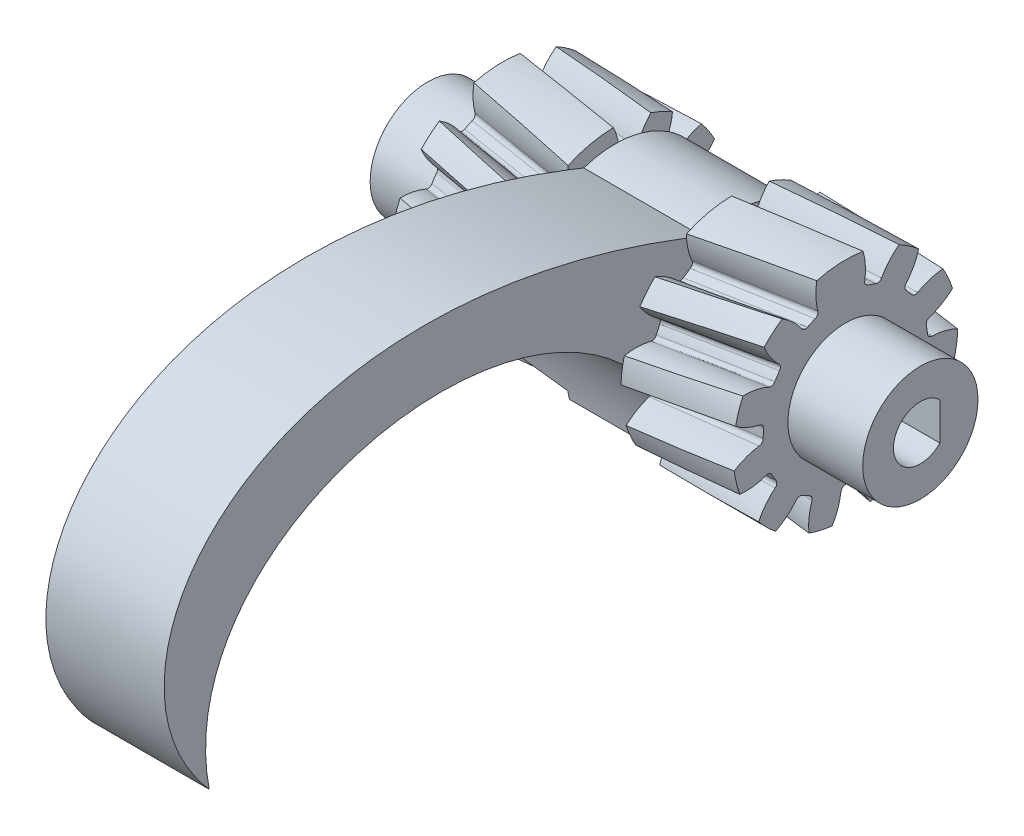
SolidWorks part; units mm, degrees
material "ABS"
ref_plane "Front Plane" through (0, 0, 0) normal (0, 0, 1) x (1, 0, 0)
ref_plane "Top Plane" through (0, 0, 0) normal (0, 1, 0) x (1, 0, 0)
ref_plane "Right Plane" through (0, 0, 0) normal (1, 0, 0) x (0, 0, -1)
sketch "Sketch1" plane through (0, 0, 0) normal (1, 0, 0) x (0, 0, -1)
  line L0 (0, 0) -> (-30, 0) construction
  line L1 (-30, 0) -> (-30, -7.5) construction
  line L2 (-30, -7.5) -> (0, 0) construction
  line L6 (-23.4, 0) -> (-23.4, -7.5) construction
  circle A2 centre (0, 0) radius 1.5 construction
  arc A3 (0, -7.5) -> (-2.4038, 7.1043) centre (0, 0) ccw
  circle A4 centre (0, 0) radius 7.5
  dimension "D2" = 3
  dimension "D4" = 7.5
  dimension "D1" = 30
  dimension "D3" = 7.5
  dimension "D5" = 6.6
extrude "ClawShape" add sketch "Sketch1" along normal mid plane 7.5
sketch "GearProfile" plane through (0, 0, 0) normal (1, 0, 0) x (0, 0, -1)
  line L0 (0, 0) -> (0, 7.5) construction
  line L1 (-0.7835, 6.4526) -> (0.7835, 6.4526) construction
  line L2 (0, 0) -> (-0.5585, 5.4716) construction
  line L3 (0, 4.3) -> (-1.4813, 8.3699) construction
  line L4 (0, 0) -> (1.7949, 7.2821) construction
  line L5 (0.7835, 6.4526) -> (2.3049, 6.0776) construction
  circle A0 centre (0, 0) radius 7.5 construction
  arc A1 (-0.5585, 5.4716) -> (-2.07, 8.2441) centre (-4.6172, 5.0573) ccw
  arc A2 (0.5585, 5.4716) -> (2.07, 8.2441) centre (4.6172, 5.0573) cw
  circle A3 centre (0, 0) radius 6.5 construction
  arc A4 (0.5585, 5.4716) -> (-0.5585, 5.4716) centre (0, 0) ccw
  circle A5 centre (0, 0) radius 2.94 construction
  arc A6 (2.07, 8.2441) -> (-2.07, 8.2441) centre (0, 0) ccw
  dimension "D3" = 5.88
  dimension "D1" = 13
  dimension "D5" = 20
  dimension "D6" = 13.846
ref_plane "Plane2" through (0, 0, 0) normal (0, 0.9709, -0.2394) x (-1, 0, 0)
sketch "Sketch4" plane through (0, 0, 0) normal (0, 1, 0) x (1, 0, 0)
  line L0 (-3.75, 7.5) -> (-3.75, -7.5) construction
  line L1 (-3.75, 0.6612) -> (3.75, -0.6612)
  line L4 (-0.1691, 0) -> (0.1691, 0) construction
  line L5 (3.75, -7.5) -> (3.75, 7.5) construction
  dimension "D1" = 10
  dimension "D2" = 7.6157
curve "HelixAngle"
sketch "Sketch5" plane through (3.75, 0, 0) normal (1, 0, 0) x (0, -0.1554, -0.9879)
  line L0 (0, 0) -> (0, 7.5) construction
  line L1 (-0.7835, 6.4526) -> (0.7835, 6.4526) construction
  line L2 (0, 0) -> (-0.5585, 5.4716) construction
  line L3 (0, 4.3) -> (-1.4813, 8.3699) construction
  line L4 (0, 0) -> (1.7949, 7.2821) construction
  line L5 (0.7835, 6.4526) -> (2.3049, 6.0776) construction
  arc A1 (-0.5585, 5.4716) -> (-2.07, 8.2441) centre (-4.6172, 5.0573) ccw
  arc A2 (0.5585, 5.4716) -> (2.07, 8.2441) centre (4.6172, 5.0573) cw
  circle A3 centre (0, 0) radius 6.5 construction
  arc A4 (0.5585, 5.4716) -> (-0.5585, 5.4716) centre (0, 0) ccw
  circle A5 centre (0, 0) radius 2.94 construction
  arc A6 (2.07, 8.2441) -> (-2.07, 8.2441) centre (0, 0) ccw
sketch "Sketch6" plane through (-3.75, 0, 0) normal (1, 0, 0) x (0, -0.3216, -0.9469)
  line L0 (0, 0) -> (0, 7.5) construction
  line L1 (-0.7835, 6.4526) -> (0.7835, 6.4526) construction
  line L2 (0, 0) -> (-0.5585, 5.4716) construction
  line L3 (0, 4.3) -> (-1.4813, 8.3699) construction
  line L4 (0, 0) -> (1.7949, 7.2821) construction
  line L5 (0.7835, 6.4526) -> (2.3049, 6.0776) construction
  arc A1 (-0.5585, 5.4716) -> (-2.07, 8.2441) centre (-4.6172, 5.0573) ccw
  arc A2 (0.5585, 5.4716) -> (2.07, 8.2441) centre (4.6172, 5.0573) cw
  circle A3 centre (0, 0) radius 6.5 construction
  arc A4 (0.5585, 5.4716) -> (-0.5585, 5.4716) centre (0, 0) ccw
  circle A5 centre (0, 0) radius 2.94 construction
  arc A6 (2.07, 8.2441) -> (-2.07, 8.2441) centre (0, 0) ccw
loft "GearCut" cut profiles "Sketch6", "Sketch5" connector at (-3.75, 8.4718, -0.6914) connector at (3.75, 8.4656, 0.7638)
fillet "GearFillet" radius 0.3 2 edges
pattern_circular "GearPattern" count 11 every 31.667 about axis through (3.75, 0, 0) along (-1, 0, 0) of "GearCut", "GearFillet"
sketch "Sketch8" plane through (-3.75, 0, 0) normal (-1, 0, 0) x (0, 0, 1)
  circle A0 centre (0, 0) radius 3.85
  dimension "D2" = 7.7
extrude "Boss-Extrude1" add sketch "Sketch8" along normal blind 5
sketch "Sketch9" plane through (3.75, 0, 0) normal (1, 0, 0) x (0, 0, -1)
  line L6 (0, 0) -> (-35, 0) construction
  line L7 (-35, 0) -> (-35, -9.3782) construction
  line L8 (-35, -9.3782) -> (0, 0) construction
  line L9 (-35, -9.3782) -> (0, -6.5)
  line L10 (-2.0833, 6.1571) -> (-31.7431, 18.1532) construction
  line L11 (-31.7431, 18.1532) -> (-44.2847, 1.1451) construction
  line L12 (-44.2847, 1.1451) -> (-35, -9.3782) construction
  circle A3 centre (0, 0) radius 1.5 construction
  arc A4 (0, -6.5) -> (-2.0833, 6.1571) centre (0, 0) ccw
  spline S0 degree 3 poles (-2.0833, 6.1571) (-31.7431, 18.1532) (-44.2847, 1.1451) (-35, -9.3782) knots 0 0 0 0 1 1 1 1
  point P8 (0, 0)
  point P9 (-15.9703, 5.4162)
  point P12 (-31.7431, 18.1532)
  point P13 (-51.3435, -2.3052)
  point P14 (-44.2847, 1.1451)
  dimension "D1" = 35
  dimension "D3" = 6.5
  dimension "D4" = 15
  dimension "D2" = 3
  dimension "D5" = 31.9939
  dimension "D6" = 21.1322
  dimension "D7" = 14.0337
extrude "Boss-Extrude2" add sketch "Sketch9" along normal blind 3.95
ref_plane "Plane1" through (7.7, 0, 0) normal (1, 0, 0) x (0, 0, -1)
mirror "Mirror1" about plane through (7.7, 0, 0) normal (1, 0, 0) of bodies 107
sketch "Sketch10" plane through (19.15, 0, 0) normal (1, 0, 0) x (0, 0, -1)
  line L0 (-1.5, 0) -> (1, 0) construction
  line L1 (1, -1.118) -> (1, 1.118) construction
  line L2 (1.3, -1.245) -> (1.3, 1.245)
  arc A0 (1, 1.118) -> (1, -1.118) centre (0, 0) ccw construction
  arc A2 (1.3, 1.245) -> (1.3, -1.245) centre (0, 0) ccw
  point P8 (1, 0)
  dimension "D1" = 3
  dimension "D2" = 2.5
  dimension "D3" = 0.3
extrude "Cut-Extrude1" cut sketch "Sketch10" against normal through all and the other way blind 10
sketch "Sketch11" plane through (11.65, 0, 0) normal (1, 0, 0) x (0, 0, -1)
  line L2 (-35, -9.3782) -> (-3.042, -6.7502)
  line L3 (-35, -9.3782) -> (-36.9206, 0.6456) construction
  line L4 (-36.9206, 0.6456) -> (-28.8426, 9.9563) construction
  line L5 (-6.1311, 9.9437) -> (-3.042, -6.7502) construction
  line L6 (-28.8426, 9.9563) -> (-6.1311, 9.9437) construction
  line L7 (-35, -9.3782) -> (-1.3404, -6.6102) construction
  spline S0 degree 4 poles (-35, -9.3782) (-36.9206, 0.6456) (-28.8426, 9.9563) (-6.1311, 9.9437) (-3.042, -6.7502) knots 0 0 0 0 0 1 1 1 1 1
  point P6 (-44.4894, -11.2235)
  point P7 (0, 0)
  point P11 (-18.7378, 11.0654)
  point P12 (-40.919, 0.9606)
  point P13 (-14.3016, 8.6624)
  point P14 (-28.8426, 9.9563)
  point P15 (-6.1311, 9.9437)
  point P16 (-36.9206, 0.6456)
  dimension "D1" = 32.0659
  dimension "D2" = 10.2062
  dimension "D3" = 16.9772
  dimension "D4" = 22.7115
  dimension "D5" = 12.3265
extrude "Cut-Extrude2" cut sketch "Sketch11" against normal up to next
equation "\"Moment Arm\"= 30mm"
equation "\"D1@Sketch1\"=\"Moment Arm\""
equation "\"D3@Sketch1\"=\"Moment Arm\"/4"
equation "\"D1@ClawShape\" = \"Moment Arm\" / 4"
equation "\"D4@Sketch1\"=\"Moment Arm\"/4"
equation "\"D5@Sketch1\"=\"Moment Arm\"*0.22"
equation "\"Motor Shaft D\"= 5.88mm"
equation "\"Motor Screw\"= 3mm"
equation "\"D2@Sketch1\"=\"Motor Screw\""
equation "\"Motor Shaft L\"= 5mm"
equation "\"D3@GearProfile\" = \"Motor Shaft D\""
equation "\"D2@GearProfile\" = \"Moment Arm\" / 30"
equation "\"Module\"= 1mm"
equation "\"Pitch D\"= \"Claw D\" - ( \"Moment Arm\" / 15 )"
equation "\"Number of Teeth\"= \"Pitch D\" / \"Module\""
equation "\"Claw D\"= \"Moment Arm\" / 2"
equation "\"D1@GearProfile\" = \"Pitch D\""
equation "\"D6@GearProfile\" = 180 / \"Number of Teeth\""
equation "\"HelixAngleAux\"= sqr ( ( ( \"Moment Arm\" / 8 ) ^ 2 ) + ( tan ( 10deg ) * ( \"Moment Arm\" / 8 ) ) ^ 2 )"
equation "\"D2@Sketch4\"=\"HelixAngleAux\"*2"
equation "\"D1@GearPattern\"=(\"Number of Teeth\"/360)*300"
equation "\"D1@Boss-Extrude2\"=\"Moment Arm\"/8+0.2mm"
